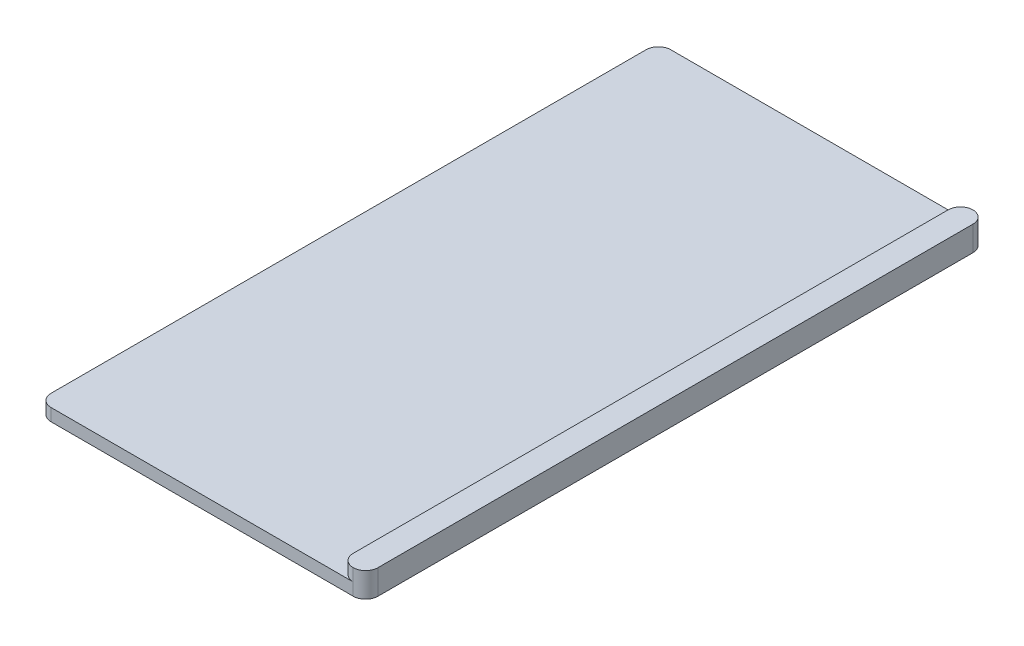
SolidWorks part; units mm, degrees
ref_plane "Front Plane" through (0, 0, 0) normal (0, 0, 1) x (1, 0, 0)
ref_plane "Top Plane" through (0, 0, 0) normal (0, 1, 0) x (1, 0, 0)
ref_plane "Right Plane" through (0, 0, 0) normal (1, 0, 0) x (0, 0, -1)
sketch "Sketch1" plane through (0, 0, 0) normal (0, 0, 1) x (1, 0, 0)
  line L0 (0, 0) -> (21.1, 0)
  line L1 (21.1, 0) -> (21.1, 1.6)
  line L2 (21.1, 1.6) -> (19.5, 1.6)
  line L3 (19.5, 1.6) -> (19.5, 0.8)
  line L4 (19.5, 0.8) -> (0, 0.8)
  line L5 (0, 0.8) -> (0, 0)
  dimension "D1" = 0.8
  dimension "D2" = 0.8
  dimension "D3" = 1.6
  dimension "D4" = 19.5
extrude "Boss-Extrude1" add sketch "Sketch1" along normal blind 40
fillet "Fillet1" radius 0.8 6 edges at (19.5, 1.2, 0) (0, 0.4, 0) (21.1, 0.8, 0) (19.5, 1.2, 40) (21.1, 0.8, 40) (0, 0.4, 40)
